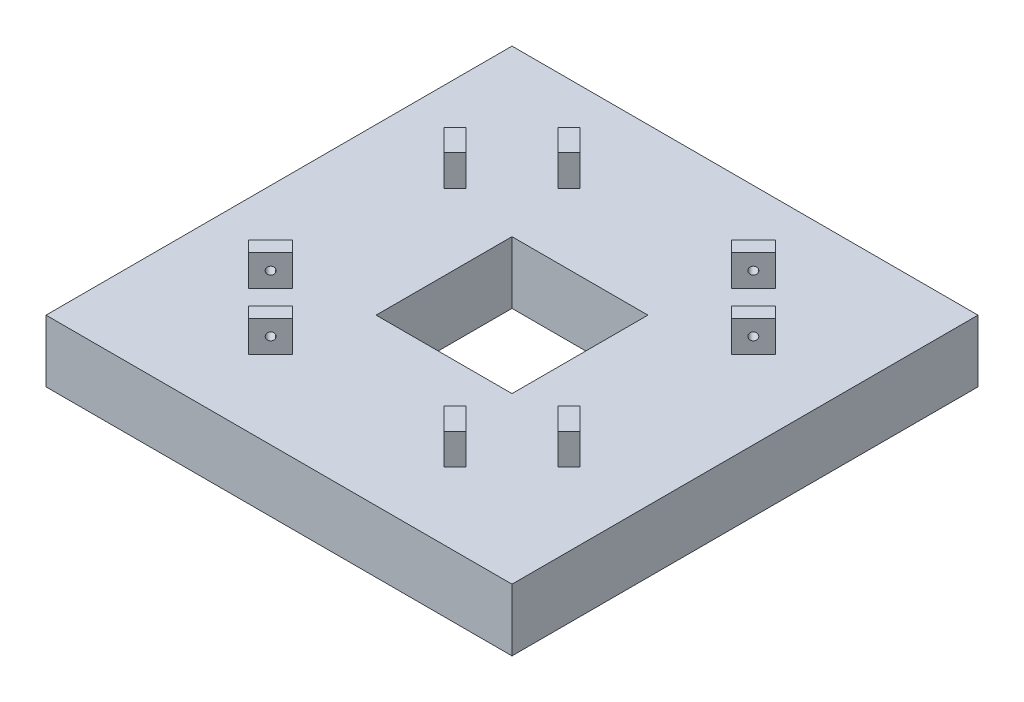
SolidWorks part; units mm, degrees
ref_plane "Front Plane" through (0, 0, 0) normal (0, 0, 1) x (1, 0, 0)
ref_plane "Top Plane" through (0, 0, 0) normal (0, 1, 0) x (1, 0, 0)
ref_plane "Right Plane" through (0, 0, 0) normal (1, 0, 0) x (0, 0, -1)
sketch "Sketch1" plane through (0, 0, 0) normal (0, 1, 0) x (1, 0, 0)
  line L1 (-381, -381) -> (381, -381)
  line L2 (-381, -381) -> (-381, 381)
  line L3 (-381, 381) -> (381, 381)
  line L4 (381, -381) -> (381, 381)
  line L5 (-381, -381) -> (381, 381) construction
  line L6 (-381, 381) -> (381, -381) construction
  point P0 (0, 0)
  dimension "D1" = 762
extrude "Boss-Extrude1" add sketch "Sketch1" along normal blind 101.6
ref_plane "Plane1" through (0, -44.45, 0) normal (0, -1, 0) x (-1, 0, 0)
sketch "Sketch3" plane through (0, 101.6, 0) normal (0, 1, 0) x (1, 0, 0)
  line L1 (-111.125, -111.125) -> (111.125, -111.125)
  line L2 (-111.125, -111.125) -> (-111.125, 111.125)
  line L3 (-111.125, 111.125) -> (111.125, 111.125)
  line L4 (111.125, -111.125) -> (111.125, 111.125)
  line L5 (-111.125, -111.125) -> (111.125, 111.125) construction
  line L6 (-111.125, 111.125) -> (111.125, -111.125) construction
  point P0 (0, 0)
  dimension "D1" = 222.25
extrude "Cut-Extrude1" cut sketch "Sketch3" against normal through all
sketch "Sketch4" plane through (0, 101.6, 0) normal (0, 1, 0) x (1, 0, 0)
  line L0 (0, 0) -> (179.3311, 179.3311) construction
  line L1 (216.8767, 141.7855) -> (141.7855, 216.8767) construction
  line L2 (141.7855, 216.8767) -> (123.825, 234.8372)
  line L3 (123.825, 234.8372) -> (159.746, 270.7583)
  line L4 (159.746, 270.7583) -> (177.7065, 252.7977)
  line L5 (177.7065, 252.7977) -> (141.7855, 216.8767)
  line L6 (216.8767, 141.7855) -> (252.7977, 177.7065)
  line L7 (252.7977, 177.7065) -> (270.7583, 159.746)
  line L8 (270.7583, 159.746) -> (234.8372, 123.825)
  line L9 (234.8372, 123.825) -> (216.8767, 141.7855)
  line L10 (111.125, -111.125) -> (111.125, 111.125) construction
  line L11 (133.5198, 199.6308) -> (40.1226, 106.2335) construction
  point P3 (115.8202, 177.1394)
  point P7 (179.3311, 179.3311)
  point P14 (234.3225, 143.3033)
  point P17 (208.1884, 159.5455)
  point P18 (0, 0)
  point P19 (143.0776, 216.4122)
  dimension "D1" = 12.7
  dimension "D2" = 50.8
  dimension "D3" = 25.4
  dimension "D4" = 6.35
extrude "Boss-Extrude2" add sketch "Sketch4" along normal blind 50.8
sketch "Sketch5" plane through (55.5061, 0, 55.5061) normal (0.7071, 0, 0.7071) x (0.7071, 0, -0.7071)
  line L0 (253.6125, 152.4) -> (304.4125, 152.4) construction
  line L1 (304.4125, 152.4) -> (304.4125, 101.6) construction
  circle A0 centre (279.0125, 127) radius 6.35
  point P4 (279.0125, 152.4)
  point P7 (304.4125, 127)
  dimension "D1" = 12.7
extrude "Cut-Extrude2" cut sketch "Sketch5" against normal through all contours A0
ref_axis "Axis1" through (0, 160.02, 0) along (0, -1, 0)
pattern_circular "CirPattern1" count 4 over 360 about axis through (0, 160.02, 0) along (0, -1, 0) of "Cut-Extrude2", "Boss-Extrude2"
